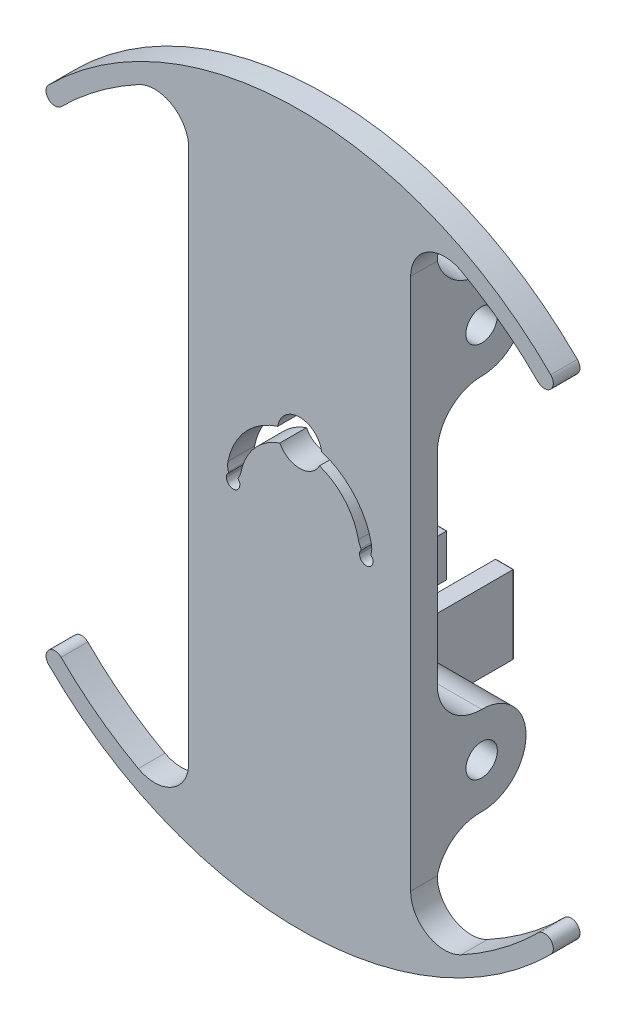
SolidWorks part; units mm, degrees
ref_plane "Front Plane" through (0, 0, 0) normal (0, 0, 1) x (1, 0, 0)
ref_plane "Top Plane" through (0, 0, 0) normal (0, 1, 0) x (1, 0, 0)
ref_plane "Right Plane" through (0, 0, 0) normal (1, 0, 0) x (0, 0, -1)
sketch "Sketch3" plane through (0, 0, 0) normal (0, 0, 1) x (1, 0, 0)
  line L0 (-35.921, -35.921) -> (-34.125, -34.125) construction
  line L1 (-15.875, -38.1) -> (0, -38.1) construction
  line L2 (-15.875, -38.1) -> (-15.875, 38.1)
  line L3 (-15.875, 38.1) -> (0, 38.1) construction
  line L4 (15.875, -38.1) -> (15.875, 38.1)
  line L5 (-15.875, -38.1) -> (15.875, 38.1) construction
  line L6 (-15.875, 38.1) -> (15.875, -38.1) construction
  line L7 (35.921, -35.921) -> (34.125, -34.125) construction
  line L8 (0, -50.8) -> (0, 50.8) construction
  line L9 (0, 38.1) -> (15.875, 38.1) construction
  line L10 (0, -38.1) -> (15.875, -38.1) construction
  line L11 (-34.125, -34.125) -> (-15.875, -15.875) construction
  line L12 (34.125, 34.125) -> (35.921, 35.921) construction
  line L13 (-15.875, -15.875) -> (0, 0) construction
  line L14 (15.875, -15.875) -> (0, 0) construction
  line L15 (-34.125, 34.125) -> (-35.921, 35.921) construction
  line L16 (34.125, -34.125) -> (15.875, -15.875) construction
  line L17 (0, 0) -> (-15.875, 15.875) construction
  line L18 (0, 0) -> (15.875, 15.875) construction
  line L19 (-15.875, 15.875) -> (-34.125, 34.125) construction
  line L20 (15.875, 15.875) -> (34.125, 34.125) construction
  arc A0 (-35.921, -35.921) -> (35.921, -35.921) centre (0, 0) ccw
  arc A1 (-34.125, -34.125) -> (-23.0827, -42.3818) centre (0, 0) ccw
  arc A2 (-15.875, 38.1) -> (-23.0827, 42.3818) centre (-20.7507, 38.1) ccw
  arc A3 (15.875, 38.1) -> (23.0827, 42.3818) centre (20.7507, 38.1) cw
  arc A4 (-15.875, -38.1) -> (-23.0827, -42.3818) centre (-20.7507, -38.1) cw
  arc A5 (15.875, -38.1) -> (23.0827, -42.3818) centre (20.7507, -38.1) ccw
  arc A6 (-35.921, 35.921) -> (-35.921, -35.921) centre (0, 0) ccw construction
  circle A7 centre (0, 0) radius 50.8 construction
  arc A8 (-34.125, 34.125) -> (-34.125, -34.125) centre (0, 0) ccw construction
  circle A9 centre (0, 0) radius 48.26 construction
  arc A10 (34.125, -34.125) -> (34.125, 34.125) centre (0, 0) ccw construction
  arc A11 (34.125, 34.125) -> (23.0827, 42.3818) centre (0, 0) ccw
  arc A12 (35.921, -35.921) -> (35.921, 35.921) centre (0, 0) ccw construction
  arc A13 (35.921, 35.921) -> (-35.921, 35.921) centre (0, 0) ccw
  arc A14 (0, 48.26) -> (-23.0827, 42.3818) centre (0, 0) ccw construction
  arc A15 (-23.0827, 42.3818) -> (-34.125, 34.125) centre (0, 0) ccw
  arc A16 (23.0827, 42.3818) -> (0, 48.26) centre (0, 0) ccw construction
  arc A17 (-23.0827, -42.3818) -> (0, -48.26) centre (0, 0) ccw construction
  arc A18 (23.0827, -42.3818) -> (34.125, -34.125) centre (0, 0) ccw
  arc A19 (0, -48.26) -> (23.0827, -42.3818) centre (0, 0) ccw construction
  arc A20 (-35.921, 35.921) -> (-34.125, 34.125) centre (-35.023, 35.023) ccw
  arc A21 (34.125, 34.125) -> (35.921, 35.921) centre (35.023, 35.023) ccw
  arc A22 (-35.921, -35.921) -> (-34.125, -34.125) centre (-35.023, -35.023) cw
  arc A23 (34.125, -34.125) -> (35.921, -35.921) centre (35.023, -35.023) cw
  point P0 (0, 0)
  point P13 (0, 0)
  point P16 (0, 0)
  point P18 (0, 0)
  dimension "D3" = 2.54
  dimension "D6" = 101.6
  dimension "D1" = 76.2
  dimension "D2" = 31.75
  dimension "D4" = 45
  dimension "D5" = 45
extrude "Main body" add sketch "Sketch3" along normal blind 3.81
ref_plane "Plane1" through (0, 0, -16.764) normal (0, 0, -1) x (-1, 0, 0)
sketch "Sketch5" plane through (15.875, 0, 0) normal (1, 0, 0) x (0, 0, -1)
  line L0 (0, 26.9938) -> (0, -26.9938)
  line L1 (0, -38.1) -> (0, 38.1) construction
  line L2 (0, 26.9938) -> (6.35, 26.9939) construction
  line L3 (6.35, 26.9939) -> (6.35, -26.9938) construction
  line L4 (6.35, -26.9938) -> (0, -26.9938) construction
  line L5 (0, 38.1) -> (0, 14.2939)
  line L6 (0, -14.2939) -> (0, -38.1)
  circle A0 centre (-0.0451, 26.9938) radius 0.0451
  arc A2 (6.35, 20.6439) -> (6.3413, 33.3438) centre (6.35, 26.9939) ccw
  arc A3 (6.0778, -33.338) -> (6.2617, -20.6445) centre (6.35, -26.9938) ccw
  arc A4 (6.35, 20.6439) -> (0, 14.2939) centre (6.3675, 14.2763) ccw
  arc A5 (6.3413, 33.3438) -> (0, 38.1) centre (6.1542, 39.6999) cw
  arc A6 (6.35, -20.6438) -> (0, -14.2939) centre (6.2623, -14.3815) cw
  arc A7 (6.35, -33.3439) -> (0, -38.1) centre (6.0797, -39.6) ccw
  arc A8 (6.3413, 33.3438) -> (0, 26.9938) centre (6.35, 26.9939) ccw construction
  arc A9 (0, 26.9938) -> (6.35, 20.6439) centre (6.35, 26.9939) ccw construction
  arc A10 (6.2617, -20.6445) -> (0, -26.9938) centre (6.35, -26.9938) ccw construction
  arc A11 (0, -26.9938) -> (6.0778, -33.338) centre (6.35, -26.9938) ccw construction
  point P5 (0, 0)
  line M6 (0, -38.1) -> (0, 38.1)
  dimension "D1" = 53.9877
  dimension "D2" = 6.35
  dimension "D3" = 12.7
  dimension "D4" = 12.7
extrude "Bosses/spacers" add sketch "Sketch5" against normal up to surface (31.75 mm away) contours A2 A5 L0 A4 M6 | A7 A3 A6 L6 M6 region at (15.875, 26.931, -5.3159) region at (15.875, -26.9385, -5.3244) up to face at (-15.875, 0, 1.905)
hole_wizard "#8 Clearance Hole1" positions "Sketch8" profile "Sketch7" hole size "#8" standard "ANSI Inch" end condition through all
sketch "Sketch8" plane through (15.875, 0, 0) normal (1, 0, 0) x (0, 0, -1)
  point P7 (6.35, 26.9939)
  point P10 (6.35, -26.8934)
sketch "Sketch7" plane through (15.875, 26.9939, -6.35) normal (0, 1, 0) x (0, 0, -1)
  line L0 (0, 0) -> (0, 52.168)
  line L1 (0, 52.168) -> (2.2479, 52.168)
  line L2 (2.2479, 52.168) -> (2.2479, 0)
  line L5 (2.2479, 0) -> (0, 0)
  line L11 (0, -6.35) -> (0, 107.95) construction
  dimension "Thru Hole Dia." = 4.4958
  dimension "Thru Hole Depth" = 52.168
sketch "Sketch26" plane through (0, 0, 0) normal (0, 0, -1) x (-1, 0, 0)
  line L6 (9.525, 0) -> (-9.525, 0) construction
  line L7 (15.875, -14.4692) -> (-15.875, -14.4692) construction
  line L8 (-15.875, -14.4692) -> (-15.875, 14.2939) construction
  line L9 (15.875, 14.2939) -> (15.875, -14.4692) construction
  line L15 (15.875, 14.2939) -> (15.875, -14.4692) construction
  line L16 (15.875, -14.4692) -> (-15.875, -14.4692) construction
  circle A0 centre (0, 9.525) radius 3.175
  arc A1 (9.525, 0) -> (-9.525, 0) centre (0, 0) ccw construction
  arc A2 (10.4775, 0) -> (-10.4775, 0) centre (0, 0) ccw
  arc A3 (8.5725, 0) -> (-8.5725, 0) centre (0, 0) ccw
  arc A4 (10.4775, 0) -> (8.5725, 0) centre (9.525, 0) cw
  arc A5 (-10.4775, 0) -> (-8.5725, 0) centre (-9.525, 0) ccw
  circle A6 centre (-9.525, 0) radius 0.9525 construction
  arc A7 (-8.5188, 0.9578) -> (-8.5607, 0.4492) centre (-8.5436, 0.7038) ccw
  arc A8 (-10.4266, 1.0318) -> (-10.4644, 0.5233) centre (-10.4486, 0.7778) cw
  circle A9 centre (9.525, 0) radius 0.9525 construction
  arc A10 (10.4268, 1.0292) -> (10.4645, 0.5226) centre (10.4487, 0.7761) ccw
  arc A11 (8.5192, 0.9548) -> (8.5608, 0.4485) centre (8.5437, 0.7019) cw
  dimension "D1" = 6.35
  dimension "D5" = 0.254
  dimension "D2" = 0.9525
  dimension "D4" = 6.35
  dimension "D6" = 0.254
  dimension "D7" = 0.254
  dimension "D8" = 0.254
  dimension "D3" = 0.9525
sketch "Sketch28" plane through (0, 0.2884, -16.764) normal (0, 0, 1) x (1, 0, 0)
  line L0 (-15.875, -20.9322) -> (-15.875, -33.6322) construction
  line L1 (-15.875, -20.9322) -> (-15.875, -33.6322) construction
  line L2 (-9.625, -21.8203) -> (-9.625, -27.8803)
  line L3 (-15.875, -32.9603) -> (-0.085, -32.9603)
  line L4 (-15.875, -32.9603) -> (-15.875, -21.8203)
  line L5 (-15.875, -21.8203) -> (-0.085, -21.8203)
  line L6 (-0.085, -32.9603) -> (-0.085, -21.8203)
  line L7 (-9.625, -27.8803) -> (-15.875, -27.8803)
  line L8 (-15.875, -30.4203) -> (-2.575, -30.4203)
  line L9 (-2.575, -30.4203) -> (-2.625, -24.8203)
  line L10 (-2.625, -24.4203) -> (-2.625, -21.8203)
  line L16 (-2.625, -24.8203) -> (-2.575, -24.8203)
  line L17 (-2.625, -29.9203) -> (-2.625, -24.8203)
  line L18 (-9.625, -30.4203) -> (-3.125, -30.4203)
  line L19 (-9.625, -21.2203) -> (-9.625, -30.4203)
  line L20 (-8.925, -21.2203) -> (-9.625, -21.2203)
  line L21 (-8.925, -21.8203) -> (-8.925, -21.2203)
  line L22 (-7.225, -21.8203) -> (-8.925, -21.8203)
  line L23 (-7.225, -23.7203) -> (-7.225, -21.8203)
  line L24 (-6.025, -23.7203) -> (-7.225, -23.7203)
  line L25 (-6.025, -21.8203) -> (-6.025, -23.7203)
  line L26 (-3.625, -21.8203) -> (-6.025, -21.8203)
  line L27 (-3.625, -21.2203) -> (-3.625, -21.8203)
  line L28 (-2.725, -21.2203) -> (-3.625, -21.2203)
  line L29 (-2.625, -24.4203) -> (-2.625, -21.3203)
  line L30 (-2.375, -24.4203) -> (-2.625, -24.4203)
  line L31 (-2.375, -24.6203) -> (-2.375, -24.4203)
  line L32 (-2.625, -24.8203) -> (-2.575, -24.8203)
  line L33 (-2.625, -29.9203) -> (-2.625, -24.8203) construction
  line L34 (-9.625, -30.4203) -> (-3.125, -30.4203) construction
  line L35 (-9.625, -21.2203) -> (-9.625, -30.4203) construction
  line L36 (-8.925, -21.2203) -> (-9.625, -21.2203) construction
  line L37 (-8.925, -21.8203) -> (-8.925, -21.2203) construction
  line L38 (-7.225, -21.8203) -> (-8.925, -21.8203) construction
  line L39 (-7.225, -23.7203) -> (-7.225, -21.8203) construction
  line L40 (-6.025, -23.7203) -> (-7.225, -23.7203) construction
  line L41 (-6.025, -21.8203) -> (-6.025, -23.7203) construction
  line L42 (-3.625, -21.8203) -> (-6.025, -21.8203) construction
  line L43 (-3.625, -21.2203) -> (-3.625, -21.8203) construction
  line L44 (-2.725, -21.2203) -> (-3.625, -21.2203) construction
  line L45 (-2.625, -24.4203) -> (-2.625, -21.3203) construction
  line L46 (-2.375, -24.4203) -> (-2.625, -24.4203)
  line L47 (-2.375, -24.6203) -> (-2.375, -24.4203)
  arc A3 (-3.125, -30.4203) -> (-2.625, -29.9203) centre (-3.125, -29.9203) ccw
  arc A4 (-3.125, -30.4203) -> (-2.625, -29.9203) centre (-3.125, -29.9203) ccw construction
  arc A5 (-2.625, -21.3203) -> (-2.725, -21.2203) centre (-2.725, -21.3203) ccw
  arc A6 (-2.625, -21.3203) -> (-2.725, -21.2203) centre (-2.725, -21.3203) ccw construction
  arc A7 (-2.575, -24.8203) -> (-2.375, -24.6203) centre (-2.575, -24.6203) ccw
  arc A8 (-2.575, -24.8203) -> (-2.375, -24.6203) centre (-2.575, -24.6203) ccw
  dimension "D2" = 2.54
  dimension "D3" = 2.54
  dimension "D4" = 2.54
  dimension "D1" = 0
extrude "Hot wire cutter base" add sketch "Sketch28" along normal up to surface (7.1752 mm away) contours A8 L32 L9 L8 L4 L3 L6 L5 L47 | L32 A8 L47 | L46 L10 | L46 L10 L5 | L8 L9 L7 L4 | L7 L5 L4 | L5 | L4 L3 L6 L5 region at (-6.1028, -25.9575, -16.764) region at (-12.75, -24.562, -16.764) region at (-12.75, -28.862, -16.764) region at (-6.375, -30.3252, -16.764) region at (-6.625, -22.482, -16.764) up to face at (0, -26.9939, -9.525)
extrude "Hot wire cutter fingers" add sketch "Sketch28<3>" against normal blind 10.16 contours L2 L7 L4 L5 | L32 A8 L47 L46 L10 L5 L6 L3 L4 L8 L9 region at (-12.75, -24.562, -16.764) region at (-6.375, -30.3252, -16.764)
sketch "Sketch28<3>" plane through (0, 0.2884, -16.764) normal (0, 0, 1) x (1, 0, 0) same geometry as "Sketch28"
fillet "Hot wire cutter fillet" radius 0.127 16 edges at (-12.75, -21.532, -26.924) (-15.875, -24.562, -26.924) (-12.75, -27.592, -26.924) (-9.625, -24.562, -26.924) (-2.6, -27.332, -26.924) (-9.225, -30.132, -26.924) (-15.875, -31.402, -26.924) (-7.98, -32.672, -26.924) (-0.085, -27.102, -26.924) (-1.355, -21.532, -26.924) (-2.625, -22.832, -26.924) (-2.5, -24.132, -26.924) (-2.375, -24.232, -26.924) (-2.4336, -24.4734, -26.924) (-15.875, -27.592, -21.844) (-15.875, -30.132, -21.844)
extrude "Monofilament slot" cut sketch "Sketch26" against normal through all contours A2 A0 | A3 A0 A2 | A0 A3 | A3 A11 A4 A2 A10 A0 | A2 A8 A5 A3 A7 A0 region at (0, 9.3688, 0) region at (-7.4018, 4.9128, 0) region at (0, 11.3064, 0) region at (0, 7.5624, 0) region at (7.4016, 4.9131, 0)
fillet "Fillet4" radius 2.54 4 edges at (-10.4268, 1.0292, 1.905) (-8.5192, 0.9548, 1.905) (10.4266, 1.0318, 1.905) (8.5188, 0.9578, 1.905)
fillet "Fillet5" radius 0.508 4 edges at (-8.5608, 0.4485, 1.905) (-10.4645, 0.5226, 1.905) (10.4644, 0.5233, 1.905) (8.5607, 0.4492, 1.905)
sketch "Sketch27" plane through (0, 0, 0) normal (0, 0, -1) x (-1, 0, 0)
  line L0 (7.62, 0) -> (-7.62, 0) construction
  text T0 "> <" font "Century Gothic" height 6.35
  point P4 (0, 0)
  dimension "D1" = 15.24
extrude "Cut-Extrude1 eyes" cut sketch "Sketch27" against normal blind 0.508
